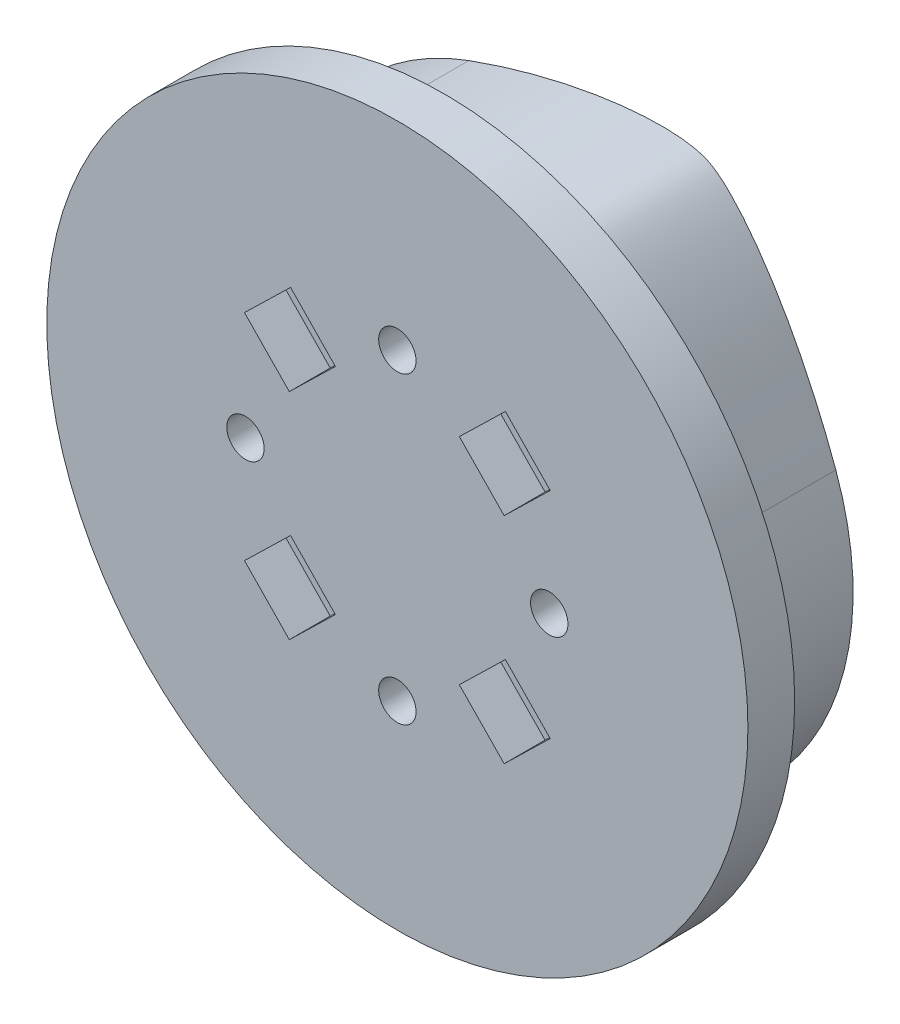
SolidWorks part; units mm, degrees
ref_plane "Front Plane" through (0, 0, 0) normal (1, 0, 0) x (0, 1, 0)
ref_plane "Top Plane" through (0, 0, 0) normal (0, 0, 1) x (0, 1, 0)
ref_plane "Right Plane" through (0, 0, 0) normal (0, 1, 0) x (-1, 0, 0)
sketch "Sketch1" plane through (0, 0, 0) normal (0, 0, 1) x (0, 1, 0)
  circle A0 centre (0, 0) radius 21
  circle A1 centre (0, 0) radius 13 construction
  circle A2 centre (0, 13) radius 1.6
  circle A3 centre (0, 13) radius 2.85
  circle A4 centre (13, 0) radius 2.85
  circle A5 centre (13, 0) radius 1.6
  circle A6 centre (0, -13) radius 2.85
  circle A7 centre (0, -13) radius 1.6
  circle A8 centre (-13, 0) radius 2.85
  circle A9 centre (-13, 0) radius 1.6
  point P19 (0, 0)
  dimension "D1" = 42
  dimension "D2" = 26
  dimension "D3" = 3.2
  dimension "D4" = 5.7
  dimension "D5" = 4
extrude "Boss-Extrude1" add sketch "Sketch1" along normal blind 10.5 contours A0 A8 A6 A4 A3 | A8 A9 | A3 A2 | A4 A5 | A6 A7 region at (0, 0, 0) region at (-13, -2.7694, 0) region at (0, 10.2306, 0) region at (13, -2.7694, 0) region at (0, -15.7694, 0)
sketch "Sketch2" plane through (0, 0, 0) normal (0, 0, -1) x (1, 0, 0)
  line L0 (0, 0) -> (0, 28.5) construction
  line L1 (0, 0) -> (12.0446, -25.8298) construction
  line L2 (0, 0) -> (-9.7476, -26.7812) construction
  line L3 (0, 0) -> (26.7812, -9.7476) construction
  line L4 (10.384, -26.6041) -> (-25.8683, -43.5089) construction
  line L5 (30.3658, -37.1246) -> (-82.3973, 3.9178) construction
  line L6 (37.1246, 30.3658) -> (-3.9178, -82.3973) construction
  circle A0 centre (0, 0) radius 28.5 construction
  circle A1 centre (0, 0) radius 24.5
  spline S0 degree 3 poles (-8.3795, -23.0225) (0.0777, -26.1007) (9.3995, -27.1075) (14.7237, -24.6248) (19.9443, -16.8367) (23.0225, -8.3795) knots 0 0 0 0 0.45 0.55 1 1 1 1
  circle M5 centre (0, 0) radius 21
  dimension "D1" = 57
  dimension "D2" = 49
  dimension "D6" = 20
  dimension "D7" = 30
  dimension "D8" = 30
  dimension "D3" = 155
  dimension "D4" = 45
  dimension "D5" = 45
  dimension "D9" = 90
  dimension "D10" = 90
  dimension "D11" = 90
extrude "Boss-Extrude3" add sketch "Sketch2" against normal up to surface (10.5 mm away) contours A1 M5 | A1 S0 region at (23.4454, 4.134, 0) region at (10.6154, 22.7398, 0) up to face at (21, 0, 10.5)
sketch "Sketch4" plane through (0, 0, 10.5) normal (0, 0, 1) x (1, 0, 0)
  circle A0 centre (0, 0) radius 30
  circle A5 centre (-13, 0) radius 1.6
  circle A6 centre (0, 13) radius 1.6
  circle A7 centre (13, 0) radius 1.6
  circle A8 centre (0, -13) radius 1.6
  dimension "D1" = 60
extrude "Boss-Extrude5" add sketch "Sketch4" along normal blind 4
sketch "Sketch3" plane through (0, 0, 0) normal (0, 0, -1) x (1, 0, 0)
  circle A0 centre (0, 0) radius 21
  circle A5 centre (-13, 0) radius 1.6
  circle A6 centre (0, 13) radius 1.6
  circle A7 centre (13, 0) radius 1.6
  circle A8 centre (0, -13) radius 1.6
  dimension "D1" = 42
extrude "Boss-Extrude4" add sketch "Sketch3" along normal blind 0.5
sketch "Sketch6" plane through (0, 0, -0.5) normal (0, 0, -1) x (1, 0, 0)
  line L0 (15.75, -2.75) -> (10.25, -2.75)
  line L1 (-2.75, 15.75) -> (2.75, 15.75)
  line L2 (-2.75, 15.75) -> (-2.75, 10.25)
  line L3 (-2.75, 10.25) -> (2.75, 10.25)
  line L4 (2.75, 15.75) -> (2.75, 10.25)
  line L5 (-2.75, 15.75) -> (2.75, 10.25) construction
  line L6 (-2.75, 10.25) -> (2.75, 15.75) construction
  line L7 (10.25, 2.75) -> (10.25, -2.75)
  line L8 (15.75, 2.75) -> (10.25, 2.75)
  line L9 (15.75, 2.75) -> (15.75, -2.75)
  line L10 (15.75, 2.75) -> (10.25, -2.75) construction
  line L11 (10.25, 2.75) -> (15.75, -2.75) construction
  line L12 (-2.75, -15.75) -> (-2.75, -10.25)
  line L13 (2.75, -10.25) -> (-2.75, -10.25)
  line L14 (2.75, -15.75) -> (2.75, -10.25)
  line L15 (2.75, -15.75) -> (-2.75, -15.75)
  line L16 (2.75, -15.75) -> (-2.75, -10.25) construction
  line L17 (2.75, -10.25) -> (-2.75, -15.75) construction
  line L18 (-15.75, 2.75) -> (-10.25, 2.75)
  line L19 (-10.25, -2.75) -> (-10.25, 2.75)
  line L20 (-15.75, -2.75) -> (-10.25, -2.75)
  line L21 (-15.75, -2.75) -> (-15.75, 2.75)
  line L22 (-15.75, -2.75) -> (-10.25, 2.75) construction
  line L23 (-10.25, -2.75) -> (-15.75, 2.75) construction
  point P0 (0, 13)
  point P21 (0, 0)
  dimension "D1" = 5.5
  dimension "D2" = 5.5
extrude "Cut-Extrude2" cut sketch "Sketch6" against normal offset from surface (3.5 mm away) 11.5 up to face at (14.6, 0, 14.5)
sketch "Sketch7" plane through (0, 0, 14.5) normal (0, 0, 1) x (1, 0, 0)
  line L0 (0, 0) -> (9.1924, 9.1924) construction
  line L1 (9.2456, 13.0807) -> (5.3041, 9.2465)
  line L2 (9.2456, 13.0807) -> (13.0807, 9.1383)
  line L3 (5.3041, 9.2465) -> (9.1392, 5.3041)
  line L4 (13.0807, 9.1383) -> (9.1392, 5.3041)
  line L5 (9.2456, 13.0807) -> (9.1392, 5.3041) construction
  line L6 (5.3041, 9.2465) -> (13.0807, 9.1383) construction
  line L7 (9.1383, -13.0807) -> (5.3041, -9.1392)
  line L8 (9.2465, -5.3041) -> (5.3041, -9.1392)
  line L9 (13.0807, -9.2456) -> (9.2465, -5.3041)
  line L10 (13.0807, -9.2456) -> (9.1383, -13.0807)
  line L11 (13.0807, -9.2456) -> (5.3041, -9.1392) construction
  line L12 (9.2465, -5.3041) -> (9.1383, -13.0807) construction
  line L13 (-13.0807, -9.1383) -> (-9.1392, -5.3041)
  line L14 (-5.3041, -9.2465) -> (-9.1392, -5.3041)
  line L15 (-9.2456, -13.0807) -> (-5.3041, -9.2465)
  line L16 (-9.2456, -13.0807) -> (-13.0807, -9.1383)
  line L17 (-9.2456, -13.0807) -> (-9.1392, -5.3041) construction
  line L18 (-5.3041, -9.2465) -> (-13.0807, -9.1383) construction
  line L19 (-9.1383, 13.0807) -> (-5.3041, 9.1392)
  line L20 (-9.2465, 5.3041) -> (-5.3041, 9.1392)
  line L21 (-13.0807, 9.2456) -> (-9.2465, 5.3041)
  line L22 (-13.0807, 9.2456) -> (-9.1383, 13.0807)
  line L23 (-13.0807, 9.2456) -> (-5.3041, 9.1392) construction
  line L24 (-9.2465, 5.3041) -> (-9.1383, 13.0807) construction
  circle A0 centre (0, 0) radius 13 construction
  circle A1 centre (9.1924, 9.1924) radius 1.6
  circle A10 centre (9.1924, -9.1924) radius 1.6
  circle A11 centre (-9.1924, -9.1924) radius 1.6
  circle A12 centre (-9.1924, 9.1924) radius 1.6
  point P18 (0, 0)
  point P34 (0, 0)
  dimension "D1" = 3.2
  dimension "D2" = 5.4988
  dimension "D3" = 5.5
extrude "Cut-Extrude3" cut sketch "Sketch7" against normal through all contours A1 | A12 | A11 | A10 region at (9.1924, 9.1924, 14.5) region at (9.1924, -9.1924, 14.5) region at (-9.1924, -9.1924, 14.5) region at (-9.1924, 9.1924, 14.5)
extrude "Cut-Extrude4" cut sketch "Sketch7<3>" against normal blind 3.5
sketch "Sketch7<3>" plane through (0, 0, 14.5) normal (0, 0, 1) x (1, 0, 0) same geometry as "Sketch7"
